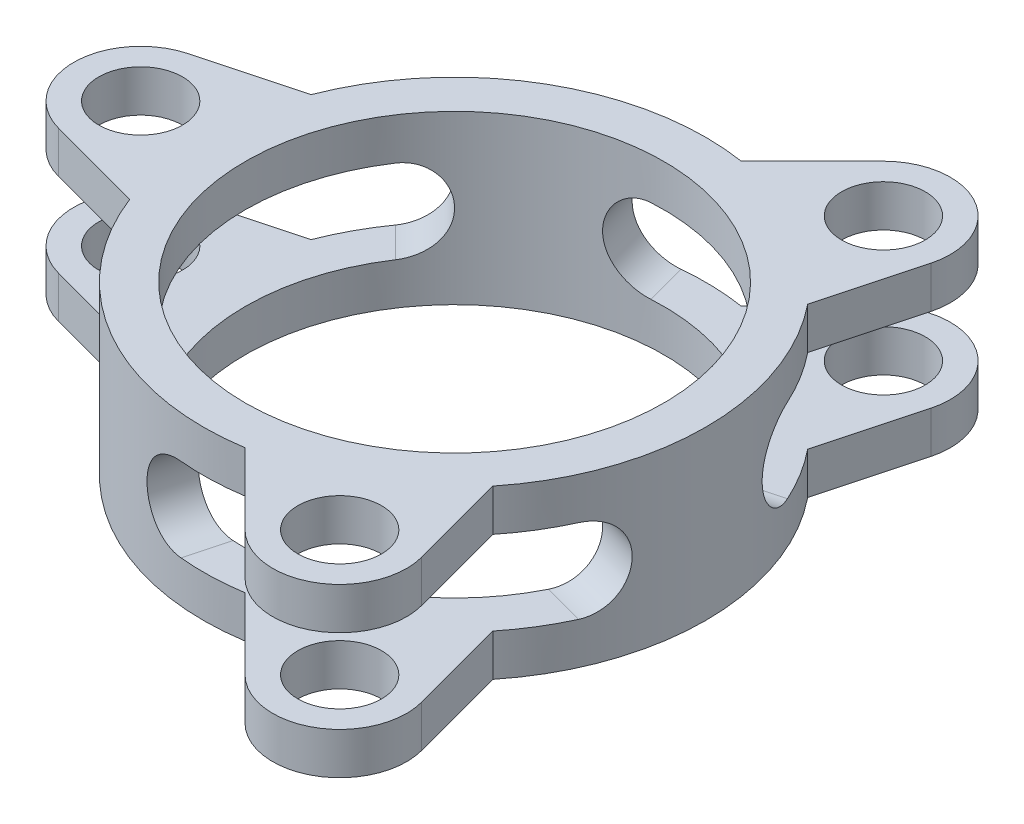
SolidWorks part; units mm, degrees
ref_plane "Front Plane" through (0, 0, 0) normal (0, 0, 1) x (1, 0, 0)
ref_plane "Top Plane" through (0, 0, 0) normal (0, 1, 0) x (1, 0, 0)
ref_plane "Right Plane" through (0, 0, 0) normal (1, 0, 0) x (0, 0, -1)
sketch "Sketch1" plane through (0, 0, 0) normal (0, 1, 0) x (1, 0, 0)
  circle A0 centre (0, 0) radius 30
  circle A1 centre (0, 0) radius 25
  dimension "D1" = 60
  dimension "D2" = 50
extrude "Boss-Extrude1" add sketch "Sketch1" along normal mid plane 20
sketch "Sketch3" plane through (0, 10, 0) normal (0, 1, 0) x (1, 0, 0)
  line L0 (0, 0) -> (-37.5, 0) construction
  line L1 (-39.5706, 7.7274) -> (-27.9753, 10.8343)
  line L2 (-39.5706, -7.7274) -> (-27.9753, -10.8343)
  line L3 (26.4774, 30.4054) -> (23.3705, 18.8101)
  line L4 (13.0931, 38.1328) -> (4.6048, 29.6445)
  line L5 (13.0931, -38.1328) -> (4.6048, -29.6445)
  line L6 (26.4774, -30.4054) -> (23.3705, -18.8101)
  circle A0 centre (0, 0) radius 37.5 construction
  circle A1 centre (-37.5, 0) radius 5
  arc A3 (-27.9753, 10.8343) -> (-27.9753, -10.8343) centre (0, 0) ccw
  arc A4 (-39.5706, 7.7274) -> (-39.5706, -7.7274) centre (-37.5, 0) ccw
  arc A5 (26.4774, 30.4054) -> (13.0931, 38.1328) centre (18.75, 32.476) ccw
  circle A6 centre (18.75, 32.476) radius 5
  arc A7 (23.3705, 18.8101) -> (4.6048, 29.6445) centre (0, 0) ccw
  arc A8 (13.0931, -38.1328) -> (26.4774, -30.4054) centre (18.75, -32.476) ccw
  circle A9 centre (18.75, -32.476) radius 5
  arc A10 (4.6048, -29.6445) -> (23.3705, -18.8101) centre (0, 0) ccw
  point P24 (0, 0)
  dimension "D1" = 75
  dimension "D2" = 8
  dimension "D3" = 10
  dimension "D4" = 60
  dimension "D5" = 15
  dimension "D6" = 15
  dimension "D7" = 3
extrude "Boss-Extrude2" add sketch "Sketch3" against normal blind 5
mirror "Mirror1" about plane through (0, 0, 0) normal (0, 1, 0) of "Boss-Extrude2"
sketch "Sketch4" plane through (0, 0, 0) normal (0, 1, 0) x (1, 0, 0)
  line L0 (0, 0) -> (18.75, -32.476) construction
  line L1 (0, 0) -> (24.1481, -6.4705) construction
  line L2 (0, 0) -> (-6.4705, -24.1481) construction
  line L3 (0, 0) -> (-37.5, 0) construction
  line L4 (0, 0) -> (18.75, 32.476) construction
  line L5 (0, 0) -> (-17.6777, -17.6777) construction
  line L6 (0, 0) -> (-17.6777, 17.6777) construction
  line L7 (0, 0) -> (-6.4705, 24.1481) construction
  line L8 (0, 0) -> (24.1481, 6.4705) construction
  line L9 (-6.4705, -24.1481) -> (-7.7646, -28.9778)
  line L10 (24.1481, -6.4705) -> (28.9778, -7.7646)
  line L11 (24.1481, 6.4705) -> (28.9778, 7.7646)
  line L12 (-6.4705, 24.1481) -> (-7.7646, 28.9778)
  line L13 (-17.6777, 17.6777) -> (-21.2132, 21.2132)
  line L14 (-17.6777, -17.6777) -> (-21.2132, -21.2132)
  arc A0 (-27.9753, -10.8343) -> (4.6048, -29.6445) centre (0, 0) ccw construction
  arc A1 (23.3705, -18.8101) -> (23.3705, 18.8101) centre (0, 0) ccw construction
  arc A2 (-21.2132, 21.2132) -> (-21.2132, -21.2132) centre (0, 0) ccw
  arc A3 (4.6048, 29.6445) -> (-27.9753, 10.8343) centre (0, 0) ccw construction
  arc A4 (-17.6777, 17.6777) -> (-17.6777, -17.6777) centre (0, 0) ccw
  circle A5 centre (0, 0) radius 25 construction
  arc A6 (-7.7646, 28.9778) -> (28.9778, 7.7646) centre (0, 0) cw
  arc A7 (-6.4705, 24.1481) -> (24.1481, 6.4705) centre (0, 0) cw
  arc A8 (28.9778, -7.7646) -> (-7.7646, -28.9778) centre (0, 0) cw
  arc A9 (24.1481, -6.4705) -> (-6.4705, -24.1481) centre (0, 0) cw
  point P29 (-37.5, -21.2132)
  point P32 (-21.2132, -21.2132)
  dimension "D1" = 45
  dimension "D2" = 90
  dimension "D3" = 45
  dimension "D4" = 45
  dimension "D5" = 90
  dimension "D6" = 45
  dimension "D7" = 45
  dimension "D8" = 90
  dimension "D9" = 45
extrude "Cut-Extrude1" cut sketch "Sketch4" against normal mid plane 10 contours A4 L13 A2 L14 | L10 A9 L9 A8 | L12 A7 L11 A6 region at (12.7182, 0, 22.0285) region at (12.7182, 0, -22.0285) region at (-25.4418, 0, 0)
fillet "Fillet3" 2 edges at (-19.4454, 5, -19.4454) (-19.4454, -5, -19.4454) type full round first side face at (-37.5, 5, 5) second side face at (-28.401, -5, 0) middle face at (-19.4454, 0, -19.4454)
fillet "Fillet4" 2 edges at (-19.4454, 5, 19.4454) (-19.4454, -5, 19.4454) type full round first side face at (-37.5, 5, 5) second side face at (-28.9465, -5, 1.0668) middle face at (-19.4454, 0, 19.4454)
fillet "Fillet5" 2 edges at (-7.1175, 5, 26.563) (-7.1175, -5, 26.563) type full round first side face at (18.75, 5, 37.476) second side face at (14.2005, -5, 24.596) middle face at (-7.1175, 0, 26.563)
fillet "Fillet6" 2 edges at (26.563, 5, 7.1175) (26.563, -5, 7.1175) type full round first side face at (18.75, 5, 37.476) second side face at (15.3971, -5, 24.535) middle face at (26.563, 0, 7.1175)
fillet "Fillet7" 2 edges at (26.563, 5, -7.1175) (26.563, -5, -7.1175) type full round first side face at (18.75, 5, -27.476) second side face at (14.2005, -5, -24.596) middle face at (26.563, 0, -7.1175)
fillet "Fillet8" 2 edges at (-7.1175, 5, -26.563) (-7.1175, -5, -26.563) type full round first side face at (18.75, 5, -27.476) second side face at (13.5493, -5, -25.6018) middle face at (-7.1175, 0, -26.563)
